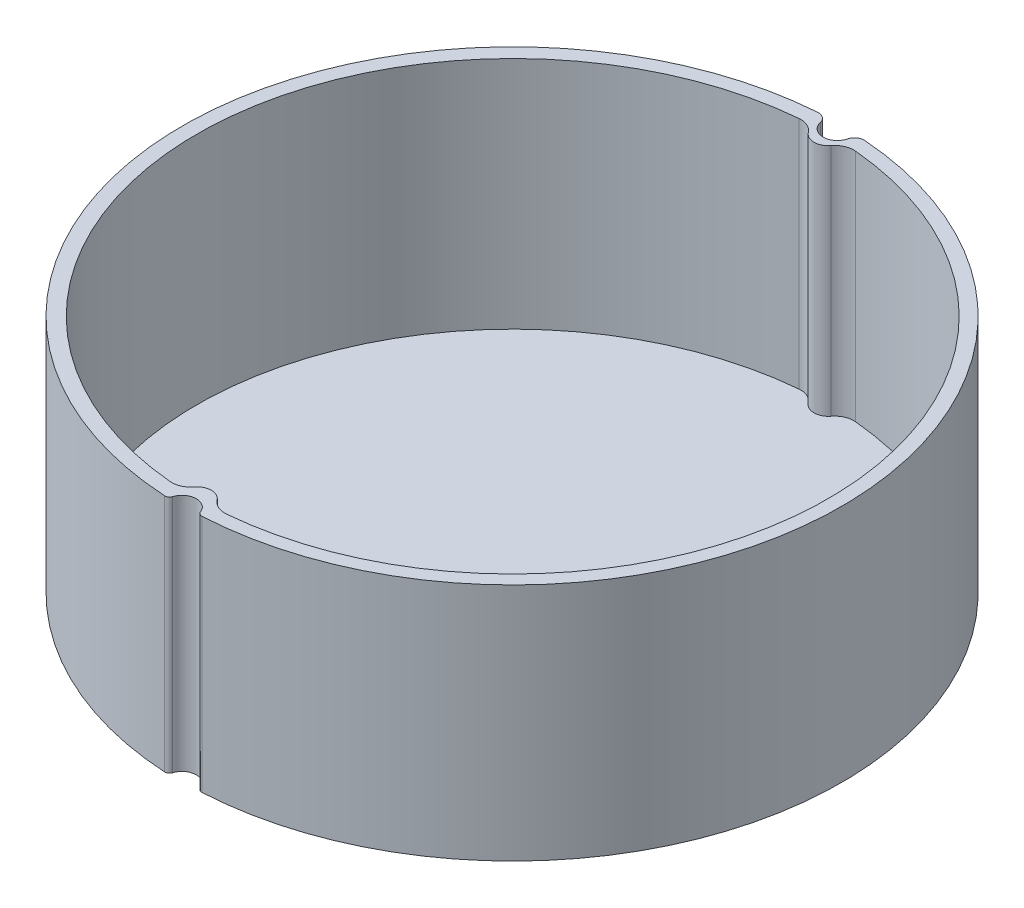
SolidWorks part; units mm, degrees
ref_plane "Front Plane" through (0, 0, 0) normal (0, 0, 1) x (1, 0, 0)
ref_plane "Top Plane" through (0, 0, 0) normal (0, 1, 0) x (1, 0, 0)
ref_plane "Right Plane" through (0, 0, 0) normal (1, 0, 0) x (0, 0, -1)
sketch "Sketch1" plane through (0, 0, 0) normal (0, 1, 0) x (1, 0, 0)
  line L3 (0, 0) -> (0, 3.1872) construction
  line L4 (0, 3.1872) -> (2.417, 3.1872)
  line L5 (0, 3.1872) -> (-2.417, 3.1872)
  arc A0 (1.8838, -34.3484) -> (34.3658, -1.5338) centre (0, 0) ccw
  circle A1 centre (0, 0) radius 37.4
  arc A2 (-2.417, 3.1872) -> (2.417, 3.1872) centre (0, 0) ccw
  circle A3 centre (0, 0) radius 34.4 construction
  arc A7 (-1.466, 33.6193) -> (1.4524, 33.5621) centre (0, 33.9371) ccw
  arc A8 (34.3658, -1.5338) -> (2.4931, 34.3095) centre (0, 0) ccw
  arc A9 (-2.5162, 34.4048) -> (-34.4624, -1.5388) centre (0, 0) ccw
  arc A10 (-34.4624, -1.5388) -> (-1.95, -34.4416) centre (0, 0) ccw
  arc A11 (1.4524, 33.5621) -> (2.4931, 34.3095) centre (2.4206, 33.3122) cw
  arc A12 (-1.466, 33.6193) -> (-2.5162, 34.4048) centre (-2.4433, 33.4075) ccw
  arc A13 (1.3882, -34.0245) -> (-1.4454, -34.0944) centre (-0.0165, -34.5507) ccw
  arc A14 (1.3882, -34.0245) -> (1.8838, -34.3484) centre (1.8564, -33.8491) ccw
  arc A15 (-1.4454, -34.0944) -> (-1.95, -34.4416) centre (-1.9217, -33.9424) cw
  point P15 (1.4997, 33.97)
  dimension "D2" = 4.834
  dimension "D3" = 4
  dimension "D4" = 34.4
  dimension "D5" = 1
  dimension "D6" = 1.5
  dimension "D7" = 0.5
  dimension "D8" = 1.5
  dimension "D9" = 1.9335
  dimension "D11" = 1.4997
sketch "Sketch2" plane through (0, 0, 0) normal (0, 1, 0) x (1, 0, 0)
  arc A0 (-32.8669, -2.9605) -> (-2.9605, -32.8669) centre (0, 0) ccw
  arc A1 (-1.1919, 32.0893) -> (1.1919, 32.0893) centre (0, 33) ccw
  arc A3 (1.1919, -32.0893) -> (-1.1919, -32.0893) centre (0, -33) ccw
  arc A5 (-2.9605, 32.8669) -> (-32.8669, -2.9605) centre (0, 0) ccw
  arc A6 (32.8669, -2.9605) -> (2.9605, 32.8669) centre (0, 0) ccw
  arc A7 (2.9605, -32.8669) -> (32.8669, -2.9605) centre (0, 0) ccw
  arc A10 (1.1919, -32.0893) -> (2.9605, -32.8669) centre (2.7811, -30.875) ccw
  arc A11 (-1.1919, -32.0893) -> (-2.9605, -32.8669) centre (-2.7811, -30.875) cw
  arc A14 (1.1919, 32.0893) -> (2.9605, 32.8669) centre (2.7811, 30.875) cw
  arc A15 (-1.1919, 32.0893) -> (-2.9605, 32.8669) centre (-2.7811, 30.875) ccw
  point P21 (1.4996, -32.9659)
  point P33 (-1.4996, 32.9659)
  dimension "D1" = 33
  dimension "D2" = 1.5
  dimension "D5" = 1.5
extrude "Boss-Extrude1" add sketch "Sketch1" along normal blind 25 contours A10 A0 A8 A7 A9 A2 L5 L4 region at (2.1157, 0, 33.4523)
extrude "Cut-Extrude2" cut sketch "Sketch2" along normal through all
extrude "Boss-Extrude2" add sketch "Sketch2<2>" along normal blind 0.5
sketch "Sketch2<2>" plane through (0, 0, 0) normal (0, 1, 0) x (1, 0, 0) same geometry as "Sketch2"
